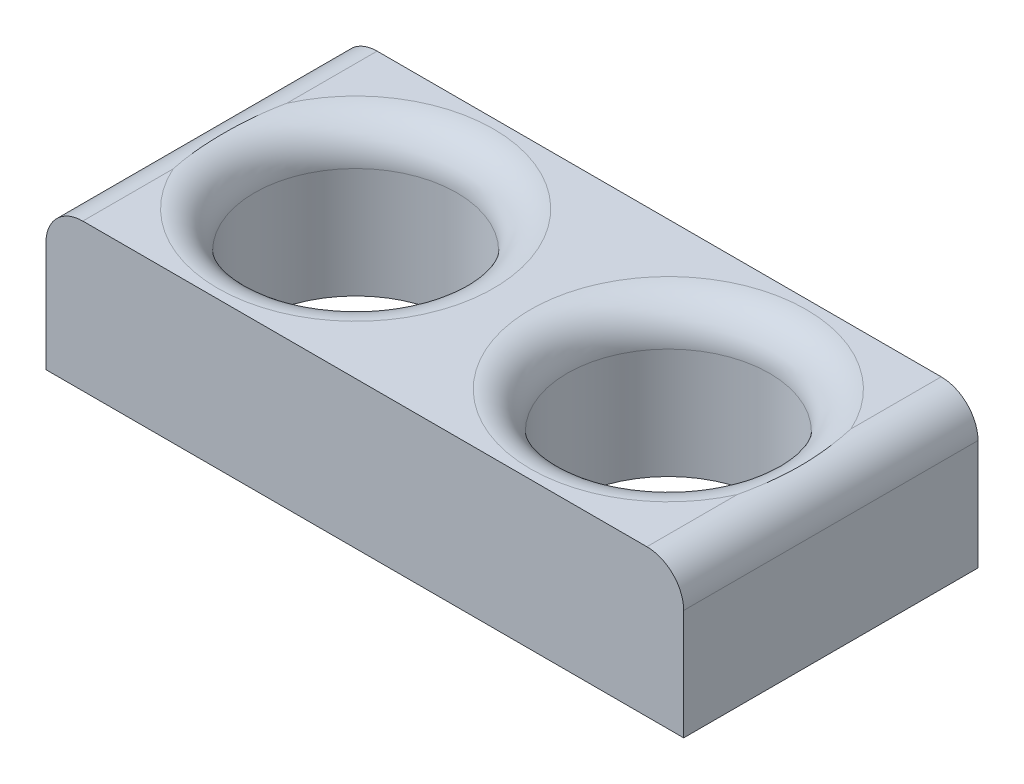
SolidWorks part; units mm, degrees
ref_plane "Front Plane" through (0, 0, 0) normal (0, 0, 1) x (1, 0, 0)
ref_plane "Top Plane" through (0, 0, 0) normal (0, 1, 0) x (1, 0, 0)
ref_plane "Right Plane" through (0, 0, 0) normal (1, 0, 0) x (0, 0, -1)
sketch "Sketch1" plane through (0, 0, 0) normal (0, 1, 0) x (1, 0, 0)
  line L0 (-12.75, 0) -> (12.75, 0) construction
  line L1 (-26, 12) -> (26, 12)
  line L2 (-26, 12) -> (-26, -12)
  line L3 (-26, -12) -> (26, -12)
  line L4 (26, 12) -> (26, -12)
  line L5 (-26, 12) -> (26, -12) construction
  line L6 (-26, -12) -> (26, 12) construction
  circle A0 centre (12.75, 0) radius 8.25
  circle A1 centre (-12.75, 0) radius 8.25
  point P0 (0, 0)
  point P9 (0, 0)
  dimension "D3" = 16.5
  dimension "D1" = 52
  dimension "D2" = 24
  dimension "D4" = 25.5
extrude "Boss-Extrude1" add sketch "Sketch1" along normal blind 12
sketch "Sketch2" plane through (0, 12, 0) normal (0, 1, 0) x (1, 0, 0)
  line L1 (-21.35, 8.85) -> (21.35, 8.85) construction
  line L2 (-21.35, 8.85) -> (-21.35, -8.85) construction
  line L3 (-21.35, -8.85) -> (21.35, -8.85) construction
  line L4 (21.35, 8.85) -> (21.35, -8.85) construction
  line L5 (-21.35, 8.85) -> (21.35, -8.85) construction
  line L6 (-21.35, -8.85) -> (21.35, 8.85) construction
  circle A0 centre (-21.35, 8.85) radius 1
  circle A1 centre (21.35, 8.85) radius 1
  circle A2 centre (21.35, -8.85) radius 1
  circle A3 centre (-21.35, -8.85) radius 1
  point P0 (0, 0)
  dimension "D3" = 2
  dimension "D1" = 17.7
  dimension "D2" = 42.7
extrude "Cut-Extrude1" cut sketch "Sketch2" against normal through all
sketch "Sketch3" plane through (0, 12, 0) normal (0, 1, 0) x (1, 0, 0)
  circle A20 centre (-21.35, 8.85) radius 1.75
  circle A21 centre (21.35, 8.85) radius 1.75
  circle A23 centre (21.35, -8.85) radius 1.75
  circle A24 centre (-21.35, -8.85) radius 1.75
  dimension "D1" = 3.5
extrude "Cut-Extrude2" cut sketch "Sketch3" against normal blind 1
sketch "Sketch4" plane through (0, 0, 0) normal (0, -1, 0) x (1, 0, 0)
  line L0 (26, -12) -> (-26, -12) construction
  line L1 (-6, -12) -> (6, -12)
  line L2 (-6, -12) -> (-6, -5)
  line L3 (-6, -5) -> (6, -5)
  line L4 (6, -12) -> (6, -5)
  line L5 (0, -5) -> (0, 0)
  line M14 (-26, -12) -> (26, -12)
  dimension "D1" = 7
  dimension "D2" = 12
extrude "Cut-Extrude3" cut sketch "Sketch4" against normal blind 5 contours L4 L3 L2 M14 region at (0, 0, -8.5)
fillet "Fillet2" radius 0.5 8 edges at (6, 2.5, -12) (0, 5, -12) (-6, 2.5, -12) (-6, 5, -8.5) (6, 5, -8.5) (6, 2.5, -5) (0, 5, -5) (-6, 2.5, -5)
sketch "Sketch6" plane through (0, 12, 0) normal (0, 1, 0) x (1, 0, 0)
  line L0 (-26, 12) -> (-26, -12) construction
  line L1 (-26, 5) -> (-36, 5)
  line L2 (-26, 5) -> (-26, -5)
  line L3 (-26, -5) -> (-36, -5)
  line L4 (-36, 5) -> (-36, -5)
  line L5 (0, 0) -> (-36, 0) construction
  line L6 (0, 0) -> (0, 20.5349) construction
  line L7 (36, 5) -> (36, -5)
  line L8 (26, -5) -> (36, -5)
  line L9 (26, 5) -> (26, -5)
  line L10 (26, 5) -> (36, 5)
  circle A0 centre (-31, 0) radius 2
  circle A1 centre (31, 0) radius 2
  dimension "D1" = 4
  dimension "D4" = 5
  dimension "D2" = 10
  dimension "D3" = 10
extrude "Boss-Extrude2" add sketch "Sketch6" against normal blind 5
fillet "Fillet3" radius 4.6 4 edges at (26, 9.5, 5) (-26, 9.5, -5) (-26, 9.5, 5) (26, 9.5, -5)
fillet "Fillet4" radius 3 4 edges at (36, 9.5, -5) (36, 9.5, 5) (-36, 9.5, 5) (-36, 9.5, -5)
sketch "Sketch9" plane through (0, 12, 0) normal (0, 1, 0) x (1, 0, 0)
  circle A0 centre (-21.35, -8.85) radius 1.75 construction
  circle A1 centre (21.35, -8.85) radius 1.75 construction
  circle A2 centre (21.35, 8.85) radius 1.75 construction
  circle A3 centre (-21.35, 8.85) radius 1.75 construction
  circle A4 centre (-21.35, -8.85) radius 1.75
  circle A5 centre (21.35, -8.85) radius 1.75
  circle A6 centre (21.35, 8.85) radius 1.75
  circle A7 centre (-21.35, 8.85) radius 1.75
extrude "Boss-Extrude3" add sketch "Sketch9" along direction (0, 1, 0) on the side against the normal up to surface (12 mm away) up to face at (-12.75, 0, 8.25)
sketch "Sketch10" plane through (0, 7, 0) normal (0, -1, 0) x (1, 0, 0)
  line L0 (-26, 12) -> (-26, -12)
  line L1 (-26, -12) -> (-39.4155, -12)
  line L2 (-39.4155, -12) -> (-39.4155, 12)
  line L3 (-39.4155, 12) -> (-26, 12)
  line L4 (26, 12) -> (41.564, 12)
  line L5 (41.564, 12) -> (41.564, -12)
  line L6 (41.564, -12) -> (26, -12)
  line L7 (26, 12) -> (26, -12) construction
  line L8 (26, -12) -> (26, 12)
extrude "Cut-Extrude4" cut sketch "Sketch10" against normal through all
fillet "Fillet5" radius 3 4 edges at (12.75, 12, 8.25) (-12.75, 12, 8.25) (26, 12, 0) (-26, 12, 0)
